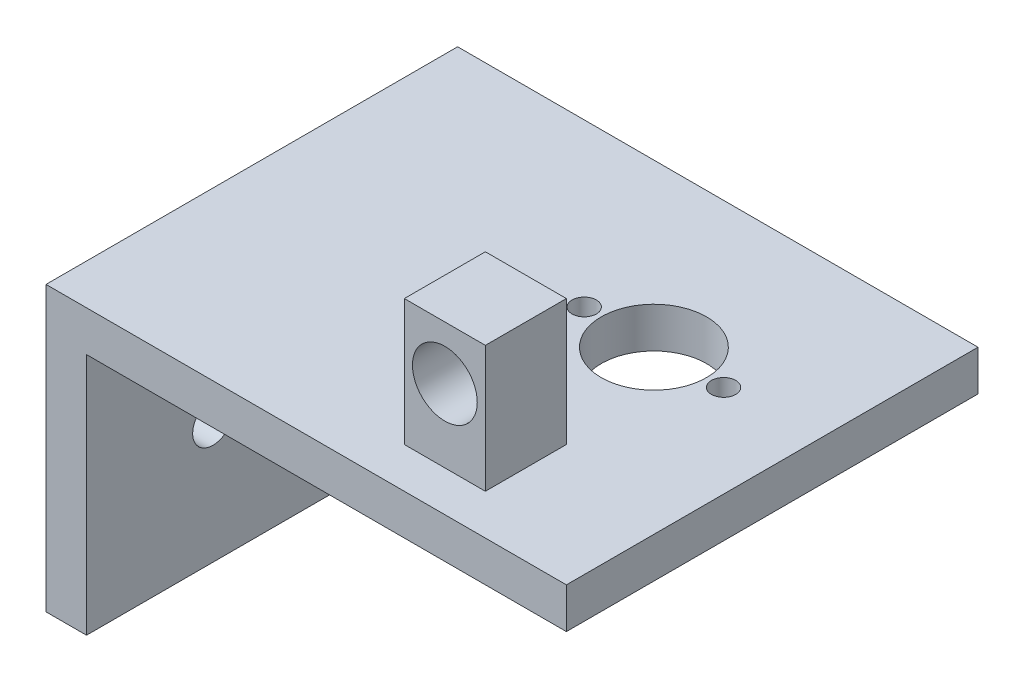
SolidWorks part; units mm, degrees
ref_plane "Front Plane" through (0, 0, 0) normal (0, 0, 1) x (1, 0, 0)
ref_plane "Top Plane" through (0, 0, 0) normal (0, 1, 0) x (1, 0, 0)
ref_plane "Right Plane" through (0, 0, 0) normal (1, 0, 0) x (0, 0, -1)
sketch "Sketch3" plane through (0, 0, 0) normal (0, 1, 0) x (1, 0, 0)
  line L1 (-20, 20) -> (20, 20)
  line L2 (-20, 20) -> (-20, -30.8)
  line L3 (-20, -30.8) -> (20, -30.8)
  line L4 (20, 20) -> (20, -30.8)
  dimension "D1" = 50.8
  dimension "D2" = 40
  dimension "D3" = 20
  dimension "D4" = 20
extrude "Boss-Extrude1" add sketch "Sketch3" along normal blind 5
sketch "Sketch4" plane through (0, 5, 0) normal (0, 1, 0) x (1, 0, 0)
  line L0 (-20, -30.8) -> (20, -30.8) construction
  line L1 (5, -15.8) -> (-5, -15.8)
  line L2 (5, -15.8) -> (5, -25.8)
  line L3 (5, -25.8) -> (-5, -25.8)
  line L4 (-5, -15.8) -> (-5, -25.8)
  dimension "D1" = 10
  dimension "D2" = 10
  dimension "D3" = 5
  dimension "D4" = 5
extrude "Boss-Extrude2" add sketch "Sketch4" along normal blind 15.6
sketch "Sketch5" plane through (0, 0, 25.8) normal (0, 0, 1) x (1, 0, 0)
  line L2 (-5, 5) -> (5, 5) construction
  circle A0 centre (0, 14) radius 4
  dimension "D1" = 8
  dimension "D2" = 9
extrude "Cut-Extrude4" cut sketch "Sketch5" against normal blind 8
sketch "Sketch6" plane through (-20, 0, 0) normal (-1, 0, 0) x (0, 0, 1)
  line L0 (-20, 5) -> (30.8, 5) construction
  line L1 (30.8, 0) -> (-20, 0)
  line L2 (30.8, 0) -> (30.8, 5)
  line L3 (30.8, 5) -> (-20, 5)
  line L4 (-20, 0) -> (-20, 5)
  dimension "D1" = 50.8
extrude "Boss-Extrude3" add sketch "Sketch6" along normal blind 24.225
sketch "Sketch8" plane through (0, 0, 0) normal (0, -1, 0) x (1, 0, 0)
  line L0 (-44.225, 30.8) -> (20, 30.8) construction
  line L1 (-44.225, -20) -> (-39.225, -20)
  line L2 (-44.225, -20) -> (-44.225, 30.8)
  line L3 (-44.225, 30.8) -> (-39.225, 30.8)
  line L4 (-39.225, -20) -> (-39.225, 30.8)
  dimension "D1" = 5
extrude "Boss-Extrude4" add sketch "Sketch8" along normal blind 30 contours L4 L3 L2 L1
sketch "Sketch9" plane through (-44.225, 0, 0) normal (-1, 0, 0) x (0, 0, 1)
  line L1 (-20, -30) -> (30.8, -30) construction
  line L3 (-20, 5) -> (-20, -30) construction
  circle A0 centre (-4.8, -15) radius 2.5
  circle A1 centre (15.2, -15) radius 2.5
  dimension "D1" = 5
  dimension "D2" = 5
  dimension "D3" = 20
  dimension "D4" = 15
  dimension "D5" = 15.2
extrude "Cut-Extrude5" cut sketch "Sketch9" against normal up to surface (5 mm away) up to face at (-39.225, -15, 5.4)
sketch "Sketch10" plane through (0, 5, 0) normal (0, 1, 0) x (1, 0, 0)
  circle A0 centre (0, 0) radius 6.5
  circle A1 centre (-8.6, 0) radius 1.5
  circle A2 centre (8.6, 0) radius 1.5
  dimension "D1" = 13
  dimension "D2" = 3
  dimension "D3" = 3
  dimension "D4" = 17.2
  dimension "D5" = 8.6
extrude "Cut-Extrude6" cut sketch "Sketch10" against normal up to surface (5 mm away) up to face at (-9.6125, 0, 5.4)
